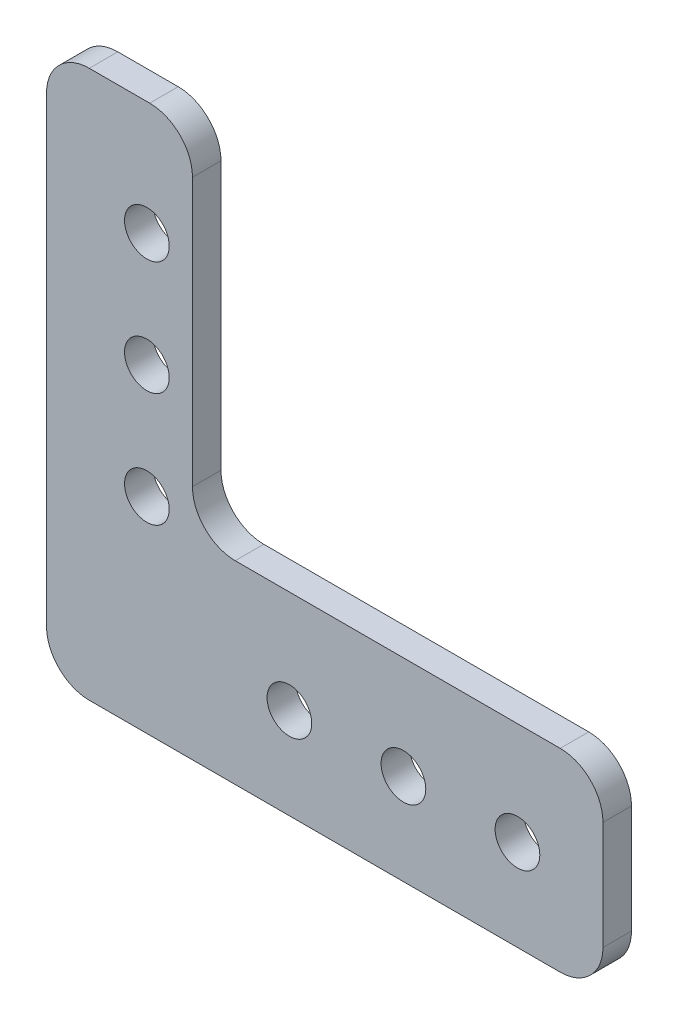
SolidWorks part; units mm, degrees
material "6061-T6 (SS)"
ref_plane "Front Plane" through (0, 0, 0) normal (0, 0, 1) x (1, 0, 0)
ref_plane "Top Plane" through (0, 0, 0) normal (0, 1, 0) x (1, 0, 0)
ref_plane "Right Plane" through (0, 0, 0) normal (1, 0, 0) x (0, 0, -1)
sketch "Sketch1" plane through (0, 0, 0) normal (0, 0, 1) x (1, 0, 0)
  line L1 (-34.925, -31.75) -> (34.925, -31.75)
  line L2 (-34.925, -31.75) -> (-34.925, 31.75)
  line L3 (-34.925, 31.75) -> (34.925, 31.75)
  line L4 (34.925, -31.75) -> (34.925, 31.75)
  line L5 (-34.925, -31.75) -> (34.925, 31.75) construction
  line L6 (-34.925, 31.75) -> (34.925, -31.75) construction
  line L7 (34.925, 31.75) -> (-10.795, 31.75)
  line L8 (34.925, 31.75) -> (34.925, -7.62)
  line L9 (34.925, -7.62) -> (-10.795, -7.62)
  line L10 (-10.795, 31.75) -> (-10.795, -7.62)
  line L11 (-34.925, -31.75) -> (-27.051, -31.75)
  line L12 (-34.925, -31.75) -> (-34.925, 31.75)
  line L13 (-34.925, 31.75) -> (-27.051, 31.75)
  line L14 (-27.051, -31.75) -> (-27.051, 31.75)
  line L15 (-27.051, -31.75) -> (34.925, -31.75)
  line L16 (-27.051, -31.75) -> (-27.051, -29.21)
  line L17 (-27.051, -29.21) -> (34.925, -29.21)
  line L18 (34.925, -31.75) -> (34.925, -29.21)
  circle A0 centre (-15.875, -19.05) radius 2.4892
  circle A1 centre (-15.875, -6.35) radius 2.4892
  circle A2 centre (-15.875, 6.35) radius 2.4892
  circle A3 centre (-15.875, 19.05) radius 2.4892
  circle A4 centre (0, -19.05) radius 2.4892
  circle A5 centre (12.7, -19.05) radius 2.4892
  circle A6 centre (25.4, -19.05) radius 2.4892
  point P0 (0, 0)
  dimension "D7" = 4.9784
  dimension "D1" = 69.85
  dimension "D2" = 63.5
  dimension "D3" = 24.13
  dimension "D4" = 24.13
  dimension "D5" = 7.874
  dimension "D6" = 63.5
  dimension "D8" = 19.05
  dimension "D9" = 12.7
  dimension "D10" = 12.7
  dimension "D11" = 12.7
  dimension "D12" = 12.7
  dimension "D13" = 12.7
  dimension "D14" = 27.051
  dimension "D15" = 12.7
  dimension "D16" = 2.54
extrude "Boss-Extrude1" add sketch "Sketch1" along normal blind 3.175 contours L14 L17 L4 L9 L10 L3 A6 A5 A4 A3 A2 A1 A0 | A0 region at (-3.4468, -8.582, 0) region at (-15.875, -19.05, 0)
fillet "Fillet1" radius 4.7625 6 edges at (-27.051, 31.75, 1.5875) (-10.795, 31.75, 1.5875) (-10.795, -7.62, 1.5875) (34.925, -7.62, 1.5875) (34.925, -29.21, 1.5875) (-27.051, -29.21, 1.5875)
